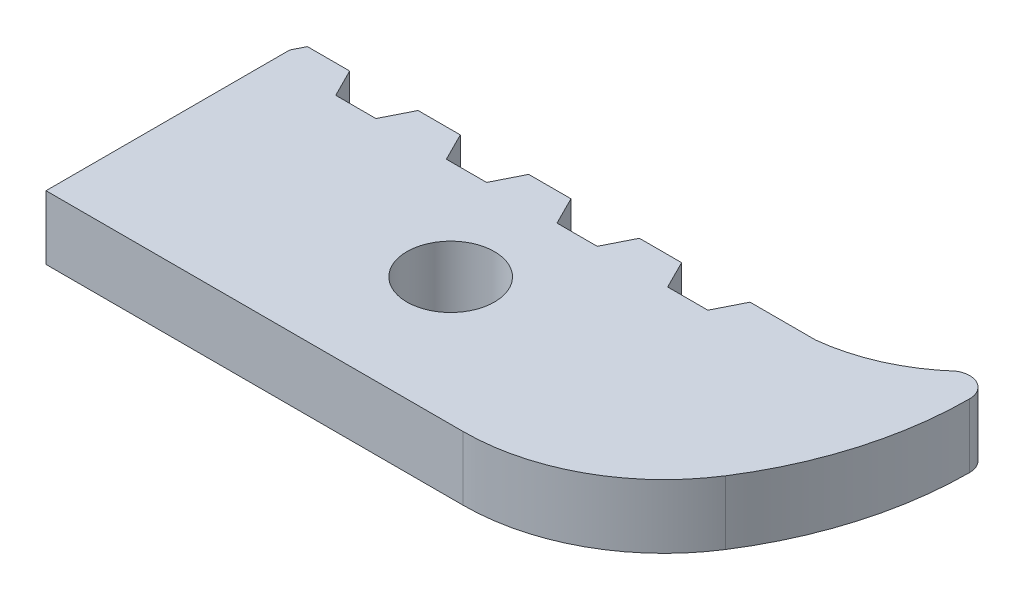
SolidWorks part; units mm, degrees
material "PET"
ref_plane "Front" through (0, 0, 0) normal (0, 0, 1) x (1, 0, 0)
ref_plane "Top" through (0, 0, 0) normal (0, 1, 0) x (1, 0, 0)
ref_plane "Right" through (0, 0, 0) normal (1, 0, 0) x (0, 0, -1)
sketch "Sketch1" plane through (0, 0, 0) normal (0, 1, 0) x (1, 0, 0)
  line L1 (-62.8447, 8.7002) -> (13.3553, 8.7002)
  line L3 (-62.8447, -3.9998) -> (13.3553, -3.9998)
  line L5 (-62.8447, 8.7002) -> (13.3553, -3.9998) construction
  line L6 (-62.8447, -3.9998) -> (13.3553, 8.7002) construction
  arc A0 (-62.8447, 8.7002) -> (-62.8447, -3.9998) centre (-62.8447, 2.3502) ccw
  arc A2 (13.3553, 8.7002) -> (13.3553, -3.9998) centre (13.3553, 2.3502) cw
  point P4 (-24.7447, 2.3502)
  dimension "D1" = 76.2
  dimension "D2" = 12.7
extrude "Boss-Extrude1" add sketch "Sketch1" along normal blind 3.175
sketch "Sketch2" plane through (0, 3.175, 0) normal (0, 1, 0) x (1, 0, 0)
  circle A0 centre (-62.8447, 2.3502) radius 2.175
  circle A1 centre (-31.0947, 2.3502) radius 2.175
  circle A2 centre (1.5553, 2.3502) radius 2.175
  arc A3 (13.3553, -3.9998) -> (13.3553, 8.7002) centre (13.3553, 2.3502) ccw construction
  dimension "D1" = 31.75
  dimension "D2" = 4.35
  dimension "D3" = 4.35
  dimension "D4" = 4.35
  dimension "D5" = 11.8
extrude "Cut-Extrude2" cut sketch "Sketch2" against normal blind 6.35 contours A1 | A0 | A2
sketch "Sketch3" plane through (0, 3.175, 0) normal (0, 1, 0) x (1, 0, 0)
  line L2 (13.3553, 8.7002) -> (13.3553, 2.3502)
  line L7 (19.7053, 2.3502) -> (19.7053, 9.9994)
  line L8 (19.7053, 2.3502) -> (13.3553, 2.3502)
  arc A0 (13.3553, -3.9998) -> (13.3553, 8.7002) centre (13.3553, 2.3502) ccw construction
  arc A2 (19.7053, 9.9994) -> (18.1741, 10.8466) centre (18.7053, 9.9994) ccw
  arc A3 (18.1741, 10.8466) -> (13.3553, 8.7002) centre (12.37, 17.3945) cw
  point P4 (25.0274, 5.3951)
  dimension "D1" = 1
  dimension "D2" = 7.6492
  dimension "D3" = 6.35
  dimension "D5" = 1.75
  dimension "D6" = 8.75
  dimension "D4" = 6.35
extrude "Boss-Extrude2" add sketch "Sketch3" against normal up to vertex (3.175 mm away) up to point (13.3553, 0, -8.7002)
sketch "Sketch4" plane through (0, 3.175, 0) normal (0, 1, 0) x (1, 0, 0)
  line L1 (19.7053, 9.9994) -> (19.7053, -6.0006)
  line L2 (19.7053, -6.0006) -> (9.2053, -6.0006)
  arc A3 (19.7053, 9.9994) -> (9.2053, -6.0006) centre (2.2054, 10.0384) cw
  arc A4 (19.7053, 9.9994) -> (18.1741, 10.8466) centre (18.7053, 9.9994) ccw construction
  dimension "D1" = 16
  dimension "D3" = 17.5
  dimension "D2" = 10.5
extrude "Cut-Extrude3" cut sketch "Sketch4" against normal blind 10
fillet "Fillet1" radius 10 1 edges at (12.6542, 1.5875, 3.9998)
sketch "Sketch5" plane through (0, 3.175, 0) normal (0, 1, 0) x (1, 0, 0)
  line L0 (-4.3147, 8.7002) -> (-0.9147, 8.7002)
  line L1 (13.3553, 8.7002) -> (-62.8447, 8.7002) construction
  line L3 (-9.8147, 8.7002) -> (-9.1147, 7.306)
  line L4 (-9.1147, 7.306) -> (-7.1147, 7.306)
  line L5 (-7.1147, 7.306) -> (-6.4147, 8.7002)
  line L14 (-4.3147, 8.7002) -> (-3.6147, 7.306)
  line L18 (-9.8147, 8.7002) -> (-6.4147, 8.7002)
  line L19 (-3.6147, 7.306) -> (-1.6147, 7.306)
  line L20 (-1.6147, 7.306) -> (-0.9147, 8.7002)
  line L21 (1.1853, 8.7002) -> (4.5853, 8.7002)
  line L22 (1.1853, 8.7002) -> (1.8853, 7.306)
  line L23 (1.8853, 7.306) -> (3.8853, 7.306)
  line L24 (3.8853, 7.306) -> (4.5853, 8.7002)
  line L25 (6.6853, 8.7002) -> (10.0853, 8.7002)
  line L26 (6.6853, 8.7002) -> (7.3853, 7.306)
  line L27 (7.3853, 7.306) -> (9.3853, 7.306)
  line L28 (9.3853, 7.306) -> (10.0853, 8.7002)
  line L29 (-15.3147, 8.7002) -> (-11.9147, 8.7002)
  line L30 (-15.3147, 8.7002) -> (-14.6147, 7.306)
  line L31 (-14.6147, 7.306) -> (-12.6147, 7.306)
  line L32 (-12.6147, 7.306) -> (-11.9147, 8.7002)
  line L33 (-20.8147, 8.7002) -> (-17.4147, 8.7002)
  line L34 (-20.8147, 8.7002) -> (-20.1147, 7.306)
  line L35 (-20.1147, 7.306) -> (-18.1147, 7.306)
  line L36 (-18.1147, 7.306) -> (-17.4147, 8.7002)
  line L37 (-26.3147, 8.7002) -> (-22.9147, 8.7002)
  line L38 (-26.3147, 8.7002) -> (-25.6147, 7.306)
  line L39 (-25.6147, 7.306) -> (-23.6147, 7.306)
  line L40 (-23.6147, 7.306) -> (-22.9147, 8.7002)
  dimension "D1" = 4
  dimension "D2" = 4
  dimension "D3" = 2
  dimension "D4" = 1.56
  dimension "D5" = 1.56
extrude "Cut-Extrude4" cut sketch "Sketch5" against normal blind 10
sketch "Sketch6" plane through (0, 3.175, 0) normal (0, 1, 0) x (1, 0, 0)
  line L0 (-62.8447, -3.9998) -> (8.5254, -3.9998) construction
  line L1 (-69.1947, 15.0502) -> (-12.2095, 15.0502)
  line L2 (-69.1947, 15.0502) -> (-69.1947, -10.3498)
  line L3 (-69.1947, -10.3498) -> (-12.2095, -10.3498)
  line L4 (-12.2095, 15.0502) -> (-12.2095, -10.3498)
  arc A1 (-62.8447, 8.7002) -> (-62.8447, -3.9998) centre (-62.8447, 2.3502) ccw construction
  dimension "D4" = 6.35
  dimension "D1" = 25.4
  dimension "D2" = 56.9852
  dimension "D3" = 6.35
extrude "Cut-Extrude5" cut sketch "Sketch6" against normal through all
